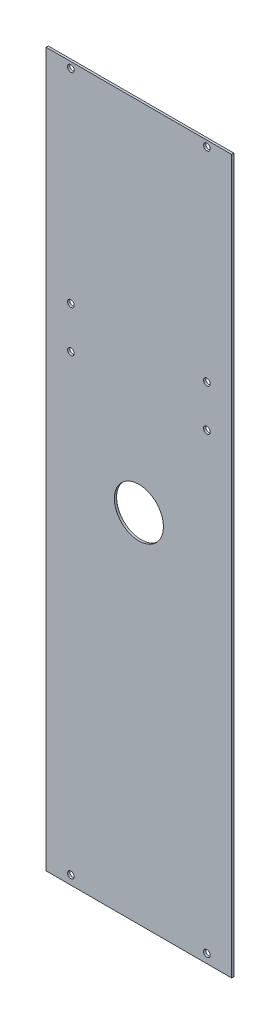
SolidWorks part; units mm, degrees
material "6061 Сплав"
ref_plane "Front Plane" through (0, 0, 0) normal (0, 0, 1) x (1, 0, 0)
ref_plane "Top Plane" through (0, 0, 0) normal (0, 1, 0) x (1, 0, 0)
ref_plane "Right Plane" through (0, 0, 0) normal (1, 0, 0) x (0, 0, -1)
sketch "Sketch1" plane through (0, 0, 0) normal (0, 0, 1) x (1, 0, 0)
  line L1 (41.6, -160) -> (-41.6, -160)
  line L2 (41.6, -160) -> (41.6, 160)
  line L3 (41.6, 160) -> (-41.6, 160)
  line L4 (-41.6, -160) -> (-41.6, 160)
  line L5 (41.6, -160) -> (-41.6, 160) construction
  line L6 (41.6, 160) -> (-41.6, -160) construction
  point P0 (0, 0)
  dimension "D1" = 83.2
  dimension "D2" = 320
extrude "Boss-Extrude1" add sketch "Sketch1" along normal blind 1
hole_wizard "Ø3.0 (3) Diameter Hole1" positions "Sketch3" profile "Sketch2" hole size "Ø3.0" standard "ANSI Metric"
sketch "Sketch3" plane through (0, 0, 1) normal (0, 0, 1) x (1, 0, 0)
  line L6 (-41.6, -160) -> (41.6, -160) construction
  line L9 (41.6, 160) -> (-41.6, 160) construction
  line L10 (0, 160) -> (0, 163.7587) construction
  line L11 (0, 160) -> (0, -152.1509) construction
  point P0 (-30.5, 66)
  point P2 (30.5, 66)
  point P15 (30.5, -156)
  point P17 (-30.5, -156)
  point P54 (-30.5, 157.3)
  point P56 (30.5, 157.3)
  point P58 (-30.5, 47.3)
  point P60 (30.5, 47.3)
  dimension "D2" = 4
  dimension "D3" = 2.7
  dimension "D4" = 4
  dimension "D5" = 30.5
  dimension "D6" = 30.5
  dimension "D7" = 94
  dimension "D8" = 30.5
  dimension "D9" = 2.7
  dimension "D10" = 94
  dimension "D11" = 30.5
  dimension "D12" = 30.5
  dimension "D13" = 30.5
  dimension "D14" = 30.5
  dimension "D15" = 30.5
  dimension "D16" = 112.7
  dimension "D17" = 112.7
sketch "Sketch2" plane through (-30.5, 66, 1) normal (1, 0, 0) x (0, -1, 0)
  line L0 (0, 0) -> (0, 1)
  line L1 (0, 1) -> (1.5, 1)
  line L2 (1.5, 1) -> (1.5, 0)
  line L5 (1.5, 0) -> (0, 0)
  line L10 (0, 1) -> (-1.5, 1) construction
  line L11 (0, -6.35) -> (0, 107.95) construction
  dimension "Hole Dia." = 3
  dimension "Hole Depth" = 1
  dimension "Drill Angle" = 180
sketch "Эскиз1" plane through (0, 0, 1) normal (0, 0, 1) x (1, 0, 0)
  circle A0 centre (0, 0) radius 11
extrude "Вырез-Вытянуть1" cut sketch "Эскиз1" against normal through all
